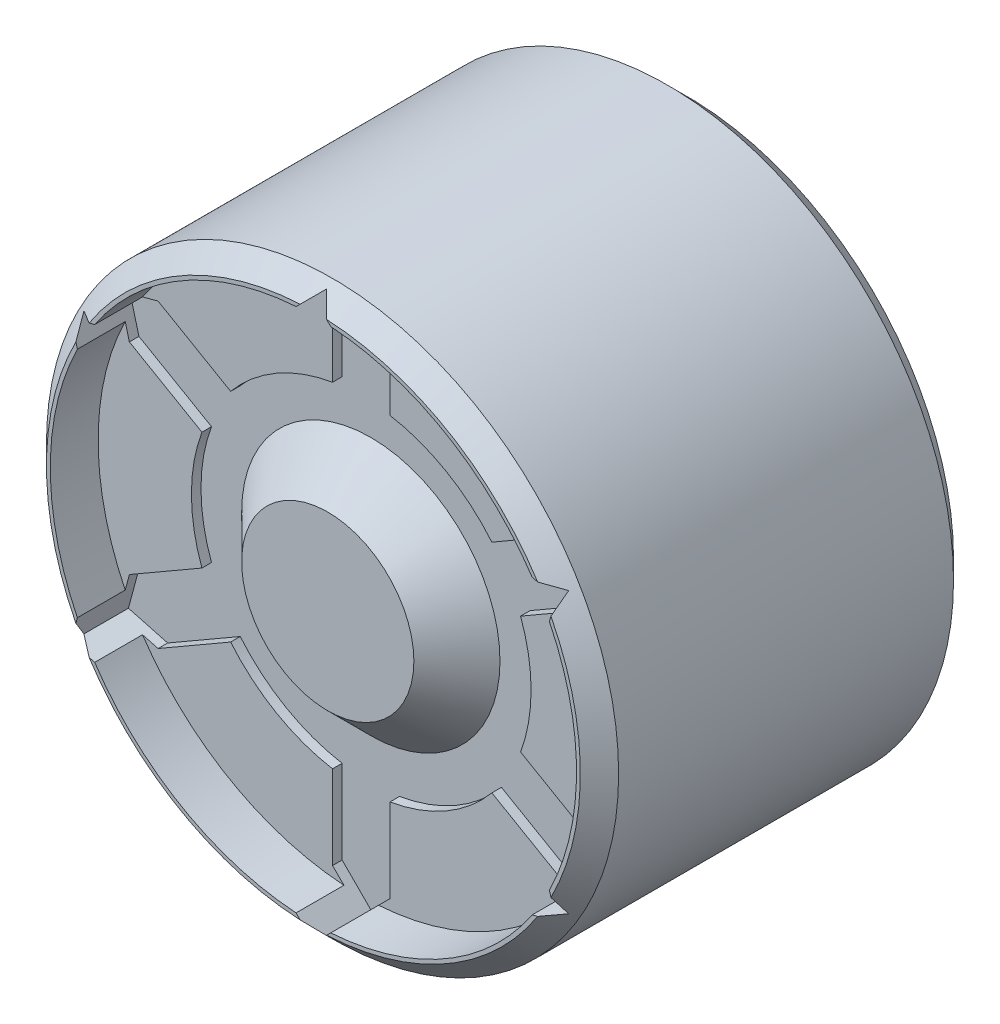
SolidWorks part; units mm, degrees
ref_plane "정면" through (0, 0, 0) normal (0, 0, 1) x (1, 0, 0)
ref_plane "윗면" through (0, 0, 0) normal (0, 1, 0) x (1, 0, 0)
ref_plane "우측면" through (0, 0, 0) normal (1, 0, 0) x (0, 0, -1)
sketch "스케치1" plane through (0, 0, 0) normal (0, 0, 1) x (1, 0, 0)
  line L0 (0, 0) -> (0, 5.85) construction
  line L1 (0, 5.85) -> (-0.6, 5.25)
  line L2 (-0.6, 5.25) -> (-0.6, 1.6705)
  line L3 (0.6, 5.25) -> (0.6, 1.6705)
  line L4 (0, 5.85) -> (0.6, 5.25)
  line L5 (4.2466, 3.1446) -> (1.1467, 1.3549)
  line L6 (5.0662, 2.925) -> (4.2466, 3.1446)
  line L7 (5.0662, 2.925) -> (4.8466, 2.1054)
  line L8 (4.8466, 2.1054) -> (1.7467, 0.3156)
  line L9 (4.8466, -2.1054) -> (1.7467, -0.3156)
  line L10 (5.0662, -2.925) -> (4.8466, -2.1054)
  line L11 (5.0662, -2.925) -> (4.2466, -3.1446)
  line L12 (4.2466, -3.1446) -> (1.1467, -1.3549)
  line L13 (0.6, -5.25) -> (0.6, -1.6705)
  line L14 (0, -5.85) -> (0.6, -5.25)
  line L15 (0, -5.85) -> (-0.6, -5.25)
  line L16 (-0.6, -5.25) -> (-0.6, -1.6705)
  line L17 (-4.2466, -3.1446) -> (-1.1467, -1.3549)
  line L18 (-5.0662, -2.925) -> (-4.2466, -3.1446)
  line L19 (-5.0662, -2.925) -> (-4.8466, -2.1054)
  line L20 (-4.8466, -2.1054) -> (-1.7467, -0.3156)
  line L21 (-4.8466, 2.1054) -> (-1.7467, 0.3156)
  line L22 (-5.0662, 2.925) -> (-4.8466, 2.1054)
  line L23 (-5.0662, 2.925) -> (-4.2466, 3.1446)
  line L24 (-4.2466, 3.1446) -> (-1.1467, 1.3549)
  circle A0 centre (0, 0) radius 1.775
  circle A1 centre (0, 0) radius 5.98
  point P36 (0, 0)
  dimension "D1" = 1.2
  dimension "D2" = 3.55
  dimension "D3" = 11.96
  dimension "D4" = 90
  dimension "D5" = 5.85
  dimension "D6" = 6
extrude "보스-돌출1" add sketch "스케치1" along normal blind 0.2 contours A1 A0 L5 L6 L7 L8 L9 L10 L11 L12 L13 L14 L15 L16 L17 L18 L19 L20 L21 L22 L23 L24 L2 L1 L4 L3 region at (-5.8109, 0, 0)
sketch "스케치2" plane through (0, 0, 0) normal (0, 0, 1) x (1, 0, 0)
  circle A0 centre (0, 0) radius 2.8
  dimension "D1" = 5.6
extrude "보스-돌출2" add sketch "스케치2" along normal blind 0.9 separate body
sketch "스케치3" plane through (0, 0, 0.2) normal (0, 0, 1) x (1, 0, 0)
  line L0 (-4.9338, -2.4306) -> (-5.0662, -2.925)
  line L1 (-5.0662, -2.925) -> (-4.8466, -2.1054) construction
  line L2 (-5.0662, -2.925) -> (-4.5719, -3.0575)
  line L3 (-5.0662, -2.925) -> (-4.2466, -3.1446) construction
  line L4 (-4.5719, 3.0575) -> (-5.0662, 2.925)
  line L5 (-5.0662, 2.925) -> (-4.9338, 2.4306)
  line L6 (0.3619, 5.4881) -> (0, 5.85)
  line L7 (0, 5.85) -> (-0.3619, 5.4881)
  line L8 (4.9338, 2.4306) -> (5.0662, 2.925)
  line L9 (5.0662, 2.925) -> (4.5719, 3.0575)
  line L10 (4.5719, -3.0575) -> (5.0662, -2.925)
  line L11 (5.0662, -2.925) -> (4.9338, -2.4306)
  line L12 (-0.3619, -5.4881) -> (0, -5.85)
  line L13 (0, -5.85) -> (0.3619, -5.4881)
  arc A0 (-4.5719, -3.0575) -> (-0.3619, -5.4881) centre (0, 0) ccw
  circle A1 centre (0, 0) radius 5.98
  circle A2 centre (0, 0) radius 5.98 construction
  arc A3 (0.3619, -5.4881) -> (4.5719, -3.0575) centre (0, 0) ccw
  arc A4 (4.9338, -2.4306) -> (4.9338, 2.4306) centre (0, 0) ccw
  arc A5 (4.5719, 3.0575) -> (0.3619, 5.4881) centre (0, 0) ccw
  arc A6 (-0.3619, 5.4881) -> (-4.5719, 3.0575) centre (0, 0) ccw
  arc A7 (-4.9338, 2.4306) -> (-4.9338, -2.4306) centre (0, 0) ccw
  point P33 (0, 0)
  dimension "D1" = 11
  dimension "D2" = 6
extrude "보스-돌출3" add sketch "스케치3" along normal blind 1
sketch "스케치4" plane through (0, 0, 0) normal (0, 0, 1) x (1, 0, 0)
  circle A0 centre (0, 0) radius 5.98
  circle A1 centre (0, 0) radius 5.98 construction
extrude "보스-돌출4" add sketch "스케치4" against normal blind 0.6
sketch "스케치6" plane through (0, 0, 0.2) normal (0, 0, 1) x (1, 0, 0)
  line L0 (0, 0) -> (0, 3.55) construction
  circle A0 centre (0, 0) radius 3.55
  circle A1 centre (0, 0) radius 2.8
  circle A2 centre (0, 0) radius 2.8 construction
  dimension "D1" = 3.55
extrude "컷-돌출2" cut sketch "스케치6" against normal blind 0.2
sketch "스케치7" plane through (0, 0, -0.6) normal (0, 0, -1) x (-1, 0, 0)
  circle A0 centre (0, 0) radius 5.98
  circle A1 centre (0, 0) radius 5.25
  circle A2 centre (0, 0) radius 5.98 construction
  dimension "D2" = 10.5
extrude "보스-돌출5" add sketch "스케치7" along normal blind 6
chamfer "모따기4" distance 1 angle 45 1 edges at (-5.25, 0, -0.6)
chamfer "모따기5" distance 0.4 angle 45 1 edges at (5.98, 0, 1.2)
chamfer "모따기6" distance 0.4 angle 45 1 edges at (-5.98, 0, -6.6)
chamfer "모따기7" distance 1 angle 45 1 edges at (2.8, 0, 0.9)
